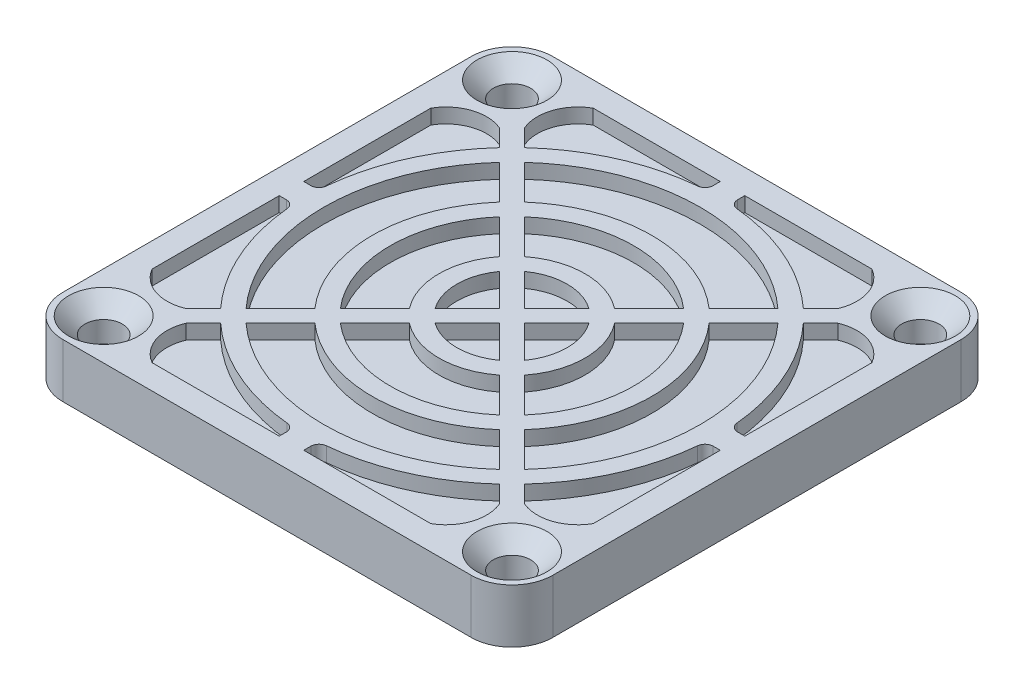
SolidWorks part; units mm, degrees
material "Custom Plastic"
ref_plane "Front" through (0, 0, 0) normal (0, 0, 1) x (1, 0, 0)
ref_plane "Top" through (0, 0, 0) normal (0, 1, 0) x (1, 0, 0)
ref_plane "Right" through (0, 0, 0) normal (1, 0, 0) x (0, 0, -1)
sketch "Sketch2" plane through (0, 0, 0) normal (0, 1, 0) x (1, 0, 0)
  line L1 (-25, 30) -> (25, 30)
  line L2 (-30, 25) -> (-30, -25)
  line L3 (-25, -30) -> (25, -30)
  line L4 (30, 25) -> (30, -25)
  line L5 (-25, 25) -> (25, 25) construction
  line L6 (-25, 25) -> (-25, -25) construction
  line L7 (-25, -25) -> (25, -25) construction
  line L8 (25, 25) -> (25, -25) construction
  arc A0 (-30, -25) -> (-25, -30) centre (-25, -25) ccw
  arc A1 (25, -30) -> (30, -25) centre (25, -25) ccw
  arc A2 (30, 25) -> (25, 30) centre (25, 25) ccw
  arc A3 (-30, 25) -> (-25, 30) centre (-25, 25) cw
  circle A4 centre (-25, 25) radius 2.285
  circle A5 centre (25, 25) radius 2.285
  circle A6 centre (-25, -25) radius 2.285
  circle A7 centre (25, -25) radius 2.285
  point P12 (0, 30)
  point P13 (-30, 0)
  dimension "D2" = 4.57
  dimension "D1" = 60
  dimension "D3" = 50
extrude "Boss-Extrude1" add sketch "Sketch2" along normal blind 6.6
sketch "Sketch3" plane through (0, 6.6, 0) normal (0, 1, 0) x (1, 0, 0)
  line L0 (0, 23.05) -> (0, 17.1) construction
  line L1 (0, 17.1) -> (0, 14.9) construction
  line L2 (0, 14.9) -> (0, 8.95) construction
  line L3 (0, 8.95) -> (0, 6.75) construction
  line L4 (0, 23.05) -> (0, 25.25) construction
  circle A0 centre (0, 0) radius 17.1
  circle A1 centre (0, 0) radius 14.9
  circle A2 centre (0, 0) radius 6.75
  circle A3 centre (0, 0) radius 8.95
  circle A4 centre (0, 0) radius 23.05
  circle A5 centre (0, 0) radius 25.25
  dimension "D1" = 13.5
  dimension "D2" = 2.2
  dimension "D3" = 50.5
extrude "Cut-Extrude1" cut sketch "Sketch3" against normal through all contours A4 A0 | A1 A3 | A2 region at (-14.4786, 6.6, 0) region at (0, 6.6, 0) region at (-22.398, 6.6, 0)
sketch "Sketch11" plane through (0, 6.6, 0) normal (0, 1, 0) x (1, 0, 0)
  line L0 (-22.6064, 24.1621) -> (24.1621, -22.6064)
  line L1 (24.1621, -22.6064) -> (22.6064, -24.1621)
  line L2 (22.6064, -24.1621) -> (-24.1621, 22.6064)
  line L3 (-24.1621, 22.6064) -> (-22.6064, 24.1621)
  line L4 (24.1621, 22.6064) -> (-22.6064, -24.1621)
  line L5 (-22.6064, -24.1621) -> (-24.1621, -22.6064)
  line L6 (-24.1621, -22.6064) -> (22.6064, 24.1621)
  line L7 (22.6064, 24.1621) -> (24.1621, 22.6064)
  line L8 (-25, 25) -> (25, -25) construction
  circle A0 centre (0, 0) radius 1.1 construction
  circle A1 centre (-25, 25) radius 2.285 construction
  circle A2 centre (25, 25) radius 2.285 construction
  circle A3 centre (-25, -25) radius 2.285 construction
  circle A4 centre (25, -25) radius 2.285 construction
  circle M2 centre (0, 0) radius 23.05
  dimension "D1" = 2.2
extrude "Boss-Extrude6" add sketch "Sketch11" against normal up to surface (6.6 mm away) contours L3 L2 L0 M2 | L2 L6 L0 M2 | L6 L2 L4 L0 | L6 L4 L2 M2 | L6 L0 L4 M2 | L0 L4 L2 M2 region at (-19.8384, 6.6, -19.8384) region at (-8.5352, 6.6, -8.5352) region at (8.5352, 6.6, -8.5352) region at (0, 6.6, 0) region at (8.5352, 6.6, 8.5352) region at (-8.5352, 6.6, 8.5352) up to face at (0, 0, 23.05)
sketch "Sketch12" plane through (0, 6.6, 0) normal (0, 1, 0) x (1, 0, 0)
  line L0 (-22.6064, 24.1621) -> (24.1621, -22.6064) construction
  line L1 (-19.181, 20.7366) -> (-17.0597, 18.6153)
  line L2 (0, 23.05) -> (0, 17.1) construction
  line L4 (-1.5, 27) -> (-1.5, 26.1307)
  line L8 (-25, -27) -> (25, -27)
  line L9 (27, -25) -> (27, 25)
  line L10 (25, 27) -> (-25, 27)
  line L11 (-27, 25) -> (-27, -25)
  line L14 (-1.5, 27) -> (-17.0597, 27)
  circle A0 centre (-25, 25) radius 2.285 construction
  circle A1 centre (-25, 25) radius 5.685 construction
  arc A2 (-17.0597, 27) -> (-19.181, 20.7366) centre (-14.588, 22.672) ccw
  arc A3 (-2.4048, 25.1352) -> (-1.5, 26.1307) centre (-2.5, 26.1307) ccw
  circle A4 centre (0, 0) radius 25.25 construction
  arc A5 (-2.4048, 25.1352) -> (-17.0597, 18.6153) centre (0, 0) ccw
  arc A8 (-27, -25) -> (-25, -27) centre (-25, -25) ccw
  arc A9 (25, -27) -> (27, -25) centre (25, -25) ccw
  arc A10 (27, 25) -> (25, 27) centre (25, 25) ccw
  arc A11 (-25, 27) -> (-27, 25) centre (-25, 25) ccw
  dimension "D2" = 3.4
  dimension "D5" = 1
  dimension "D3" = 1.5
  dimension "D4" = 3
  dimension "D1" = 3
extrude "Cut-Extrude3" cut sketch "Sketch12" against normal through all
ref_plane "Plane2" through (-25, 6.6, -25) normal (0.7071, 0, -0.7071) x (-0.7071, 0, -0.7071)
mirror "Mirror2" about plane through (-25, 6.6, -25) normal (0.7071, 0, -0.7071) of "Cut-Extrude3"
pattern_circular "CirPattern1" count 4 over 360 about axis through (0, 0, 0) along (0, 1, 0) of "Cut-Extrude3", "Mirror2"
ref_plane "Plane1" through (0, 3.3, 0) normal (0, 1, 0) x (-1, 0, 0)
sketch "Sketch5" plane through (0, 3.3, 0) normal (0, -1, 0) x (1, 0, 0)
  line L0 (-28.05, 0) -> (28.05, 0) construction
  line L1 (-21.9902, 28.05) -> (21.9902, 28.05)
  line L2 (-28.05, 21.9902) -> (-28.05, -21.9902)
  line L3 (-21.9902, -28.05) -> (21.9902, -28.05)
  line L4 (28.05, 21.9902) -> (28.05, -21.9902)
  line L5 (0, 28.05) -> (0, -28.05) construction
  arc A4 (-21.9902, 28.05) -> (-28.05, 21.9902) centre (-25, 25) cw
  arc A5 (21.9902, 28.05) -> (28.05, 21.9902) centre (25, 25) ccw
  arc A6 (28.05, -21.9902) -> (21.9902, -28.05) centre (25, -25) ccw
  arc A7 (-28.05, -21.9902) -> (-21.9902, -28.05) centre (-25, -25) cw
  circle A11 centre (-25, -25) radius 2.285 construction
  circle A13 centre (-25, 25) radius 2.285 construction
  circle A14 centre (25, 25) radius 2.285 construction
  circle A15 centre (25, -25) radius 2.285 construction
  dimension "D2" = 2
  dimension "D1" = 56.1
extrude "Cut-Extrude2" cut sketch "Sketch5" against normal offset from surface 1.8 and the other way offset from surface 2.82 up to face at (24.34, 6.6, 10.0388) other way up to face at (24.34, 0, 10.0388)
extrude "Cut-Extrude-Thin1" cut sketch "Sketch5<3>" along normal through all and the other way up to surface (1.5 mm away) thin other way up to face at (17.5131, 4.8, 0) thin type one direction wall 0.05
sketch "Sketch5<3>" plane through (0, 3.3, 0) normal (0, -1, 0) x (1, 0, 0) same geometry as "Sketch5"
sketch "Sketch9" plane through (0, 3.3, 0) normal (0, 1, 0) x (-1, 0, 0)
  line L0 (-28.05, 20.715) -> (-25, 20.715)
  line L1 (-20.715, 25) -> (-20.715, 28.05)
  line L3 (20.715, 28.05) -> (20.715, 25)
  line L4 (21.9902, 28.05) -> (-21.9902, 28.05)
  line L5 (20.715, 28.05) -> (-20.715, 28.05)
  line L6 (-28.05, 21.9902) -> (-28.05, -21.9902)
  line L7 (-28.05, 20.715) -> (-28.05, -20.715)
  line L8 (-21.9902, -28.05) -> (21.9902, -28.05)
  line L9 (-20.715, -28.05) -> (20.715, -28.05)
  line L10 (28.05, -21.9902) -> (28.05, 21.9902)
  line L11 (28.05, -20.715) -> (28.05, 20.715)
  line L12 (25, 20.715) -> (28.05, 20.715)
  line L14 (28.05, -20.715) -> (25, -20.715)
  line L15 (20.715, -25) -> (20.715, -28.05)
  line L17 (-20.715, -28.05) -> (-20.715, -25)
  line L18 (-25, -20.715) -> (-28.05, -20.715)
  arc A4 (-28.05, 21.9902) -> (-21.9902, 28.05) centre (-25, 25) ccw
  arc A5 (-25, 20.715) -> (-20.715, 25) centre (-25, 25) ccw
  arc A6 (-21.9902, -28.05) -> (-28.05, -21.9902) centre (-25, -25) ccw
  arc A7 (-20.715, -25) -> (-25, -20.715) centre (-25, -25) ccw
  arc A8 (28.05, -21.9902) -> (21.9902, -28.05) centre (25, -25) ccw
  arc A9 (25, -20.715) -> (20.715, -25) centre (25, -25) ccw
  arc A10 (21.9902, 28.05) -> (28.05, 21.9902) centre (25, 25) ccw
  arc A11 (20.715, 25) -> (25, 20.715) centre (25, 25) ccw
  dimension "D1" = 0
extrude "Boss-Extrude5" add sketch "Sketch9" along normal mid plane 2.8 separate body
fillet "Fillet1" radius 1 8 edges at (-21.9902, 1.41, 28.05) (-28.05, 1.41, 21.9902) (28.05, 1.41, 21.9902) (21.9902, 1.41, 28.05) (28.05, 1.41, -21.9902) (21.9902, 1.41, -28.05) (-21.9902, 1.41, -28.05) (-28.05, 1.41, -21.9902)
chamfer "Chamfer1" distance 2 angle 45 8 edges at (-25, 6.6, -22.715) (25, 6.6, -22.715) (25, 6.6, 27.285) (-25, 6.6, 27.285) (25, 0, 27.285) (-25, 0, 27.285) (-25, 0, -22.715) (25, 0, -22.715)
sketch "Sketch7" plane through (0, 0, 0) normal (0, 0, 1) x (1, 0, 0)
  line L1 (-28.04, 0) -> (-28.1, 0)
  line L2 (-28.04, 0) -> (-28.1, 0.4)
  line L4 (-28.1, 0) -> (-28.1, 0.4)
  dimension "D1" = 0.4
  dimension "D2" = 0.06
extrude "Boss-Extrude3" add sketch "Sketch7" along normal mid plane 7
mirror "Mirror1" about plane through (0, 0, 0) normal (1, 0, 0) of "Boss-Extrude3"
sketch "Sketch10" plane through (0, 0, 0) normal (0, 1, 0) x (1, 0, 0)
  line L0 (-30, 30) -> (30, -30) construction
  line L1 (-30, 30) -> (30, 30)
  line L2 (-30, 30) -> (-30, -30)
  line L3 (-30, -30) -> (30, -30)
  line L4 (30, 30) -> (30, -30)
  dimension "D1" = 60
delete or keep bodies "Plastic" [suppressed] type delete bodies bodies 127 140
